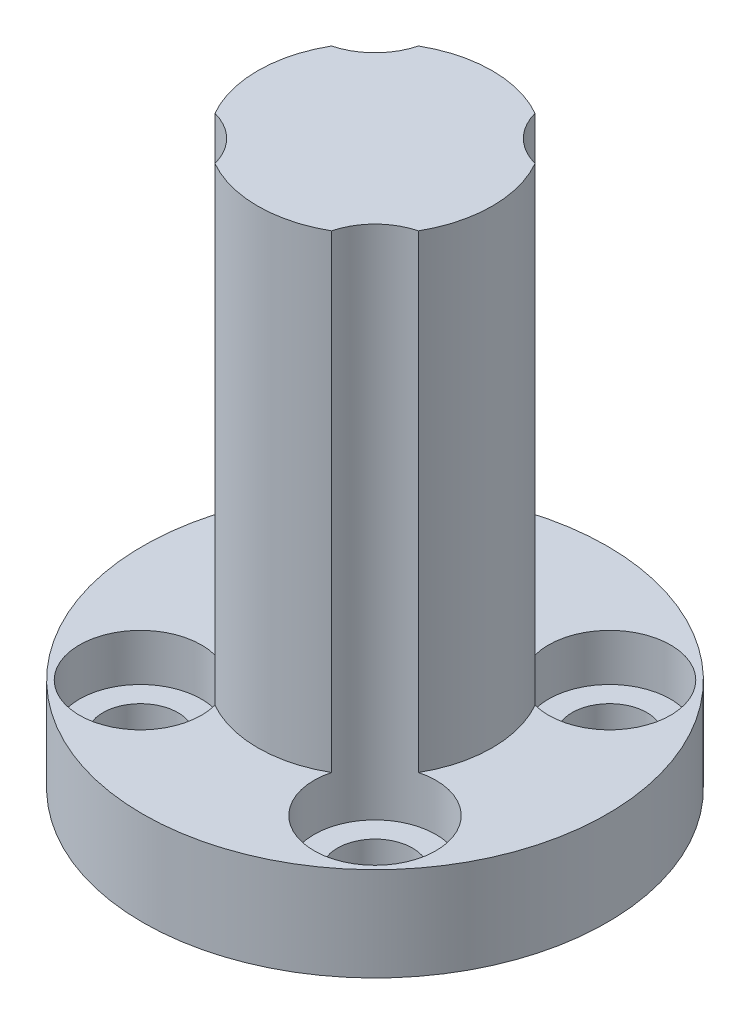
SolidWorks part; units mm, degrees
ref_plane "Front Plane" through (0, 0, 0) normal (0, 0, 1) x (1, 0, 0)
ref_plane "Top Plane" through (0, 0, 0) normal (0, 1, 0) x (1, 0, 0)
ref_plane "Right Plane" through (0, 0, 0) normal (1, 0, 0) x (0, 0, -1)
sketch "Sketch1" plane through (0, 0, 0) normal (0, 1, 0) x (1, 0, 0)
  circle A0 centre (0, 0) radius 9.9
  dimension "D1" = 19.8
extrude "Boss-Extrude1" add sketch "Sketch1" along normal blind 4 contours A0
sketch "Sketch2" plane through (0, 4, 0) normal (0, 1, 0) x (1, 0, 0)
  circle A0 centre (0, 0) radius 5
  dimension "D1" = 10
extrude "Boss-Extrude2" add sketch "Sketch2" along normal blind 20
sketch "Sketch3" plane through (0, 4, 0) normal (0, 1, 0) x (1, 0, 0)
  line L0 (-5, 5) -> (5, -5) construction
  line L1 (5, 5) -> (-5, -5) construction
  circle A0 centre (-5, 5) radius 1.6
  circle A1 centre (5, 5) radius 1.6
  circle A2 centre (5, -5) radius 1.6
  circle A3 centre (-5, -5) radius 1.6
  circle A4 centre (5, 5) radius 2.6
  circle A5 centre (-5, 5) radius 2.6
  circle A6 centre (-5, -5) radius 2.6
  circle A7 centre (5, -5) radius 2.6
  point P20 (0, 0)
  dimension "D3" = 3.2
  dimension "D4" = 5.2
  dimension "D1" = 10
  dimension "D2" = 10
extrude "Cut-Extrude1" cut sketch "Sketch3" against normal up to next contours A1 | A2 | A3 | A0 region at (-5, 4, -5) region at (5, 4, -5) region at (5, 4, 5) region at (-5, 4, 5)
extrude "Cut-Extrude2" cut sketch "Sketch3<3>" along normal up to next
sketch "Sketch3<3>" plane through (0, 4, 0) normal (0, 1, 0) x (1, 0, 0) same geometry as "Sketch3"
extrude "Cut-Extrude3" cut sketch "Sketch3<4>" against normal blind 2
sketch "Sketch3<4>" plane through (0, 4, 0) normal (0, 1, 0) x (1, 0, 0) same geometry as "Sketch3"
